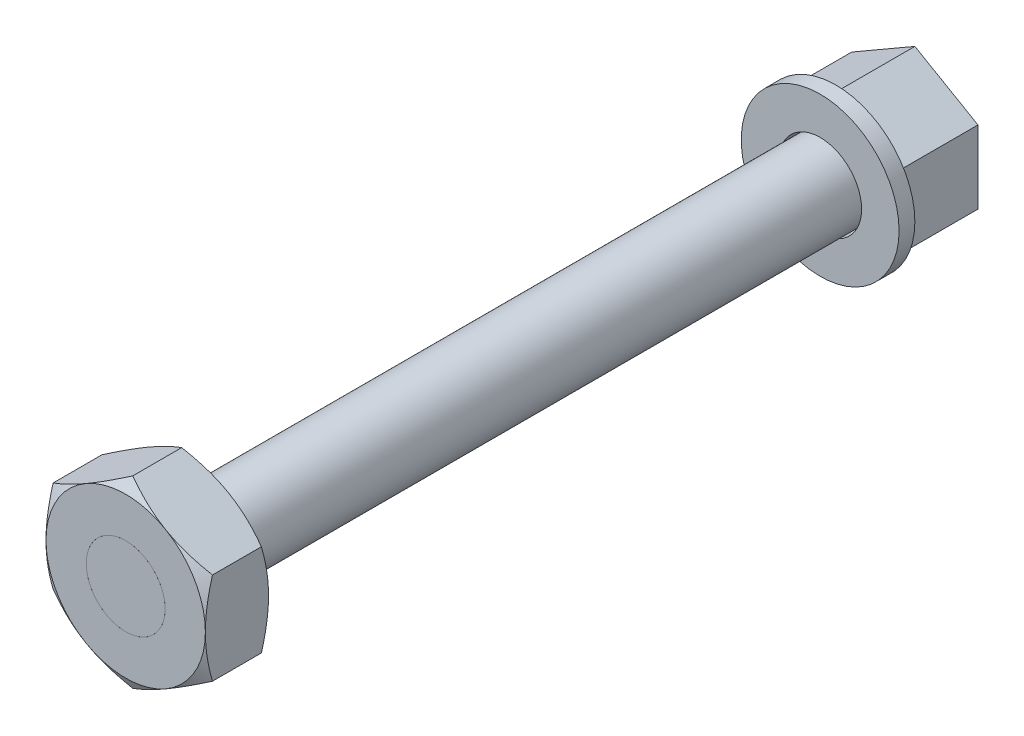
SolidWorks part; units mm, degrees
other "Dado"
other "Rosetta"
other "Vite"
ref_plane "Piano frontale" through (0, 0, 0) normal (0, 0, 1) x (1, 0, 0)
ref_plane "Piano superiore" through (0, 0, 0) normal (0, 1, 0) x (1, 0, 0)
ref_plane "Piano destro" through (0, 0, 0) normal (1, 0, 0) x (0, 0, -1)
sketch "Sketch1" plane through (0, 0, 0) normal (0, 0, 1) x (1, 0, 0)
  line L1 (-3.1632, 12.1549) -> (-11.1632, 16.7737)
  line L2 (-11.1632, 16.7737) -> (-19.1632, 12.1549)
  line L3 (-19.1632, 12.1549) -> (-19.1632, 2.9173)
  line L4 (-19.1632, 2.9173) -> (-11.1632, -1.7015)
  line L5 (-11.1632, -1.7015) -> (-3.1632, 2.9173)
  line L6 (-3.1632, 2.9173) -> (-3.1632, 12.1549)
  circle A0 centre (-11.1632, 7.5361) radius 8 construction
  circle A1 centre (-11.1632, 7.5361) radius 5
  dimension "D1" = 10
  dimension "D2" = 16
extrude "Boss-Extrude1" add sketch "Sketch1" along normal blind 10 contours A1 | L5 L6 L1 L2 L3 L4 A1 region at (-3.4076, 7.5361, 0) region at (-11.1632, 7.5361, 0)
extrude "Boss-Extrude2" add sketch "Sketch1<3>" along normal blind 90 from surface contours A1 region at (-11.1632, 7.5361, 0) starting at face at (-11.1632, 7.5361, 10)
sketch "Sketch1<3>" plane through (0, 0, 0) normal (0, 0, 1) x (1, 0, 0) same geometry as "Sketch1"
sketch "Sketch3" plane through (0, 0, 0) normal (0, 0, 1) x (1, 0, 0)
  circle A0 centre (-11.1632, 7.5361) radius 10
  circle A1 centre (-11.1632, 7.5361) radius 5 construction
  circle A2 centre (-11.1632, 7.5361) radius 5.25
  dimension "D1" = 20
  dimension "D2" = 10.5
extrude "Boss-Extrude3" add sketch "Sketch3" along normal blind 2 from surface separate body starting at face at (-6.1632, 7.5361, 10)
sketch "Sketch4" plane through (0, 0, 100) normal (0, 0, 1) x (1, 0, 0)
  line L7 (-19.1632, 12.1549) -> (-19.1632, 2.9173) construction
  line L8 (-11.1632, -4.1236) -> (-1.0656, 1.7062)
  line L9 (-1.0656, 1.7062) -> (-1.0656, 13.366)
  line L10 (-1.0656, 13.366) -> (-11.1632, 19.1958)
  line L11 (-11.1632, 19.1958) -> (-21.2608, 13.366)
  line L12 (-21.2608, 13.366) -> (-21.2608, 1.7062)
  line L13 (-21.2608, 1.7062) -> (-11.1632, -4.1236)
  circle A3 centre (-11.1632, 7.5361) radius 10.0976 construction
  circle A4 centre (-11.1632, 7.5361) radius 5 construction
  circle A5 centre (-11.1632, 7.5361) radius 5
extrude "Boss-Extrude4" add sketch "Sketch4" against normal blind 8 separate body
ref_plane "Plane1" through (0, 7.5361, 0) normal (0, -1, 0) x (-1, 0, 0)
sketch "Sketch5" plane through (0, 7.5361, 0) normal (0, -1, 0) x (-1, 0, 0)
  line L0 (28.189, -96) -> (14.3326, -104)
  line L1 (14.3326, -104) -> (14.3326, -108.5)
  line L2 (14.3326, -108.5) -> (39.3326, -108.5)
  line L3 (39.3326, -108.5) -> (39.3326, -83.5)
  line L4 (39.3326, -83.5) -> (14.3326, -83.5)
  line L5 (14.3326, -83.5) -> (14.3326, -88)
  line L6 (14.3326, -88) -> (28.189, -96)
  line L7 (14.3326, -104) -> (20.4964, -104) construction
  line L8 (14.3326, -88) -> (20.7305, -88) construction
  point P7 (21.2608, -100)
  point P10 (21.2608, -92)
  dimension "D1" = 30
  dimension "D2" = 30
  dimension "D3" = 25
  dimension "D4" = 25
ref_plane "Plane2" through (-11.1632, 0, 0) normal (1, 0, 0) x (0, 0, -1)
ref_axis "Axis1" through (-11.1632, 7.5361, 51.6) along (0, 0, 1)
revolve "Cut-Revolve1" cut sketch "Sketch5" angle 360 about axis through (-11.1632, 7.5361, 51.6) along (0, 0, 1)
